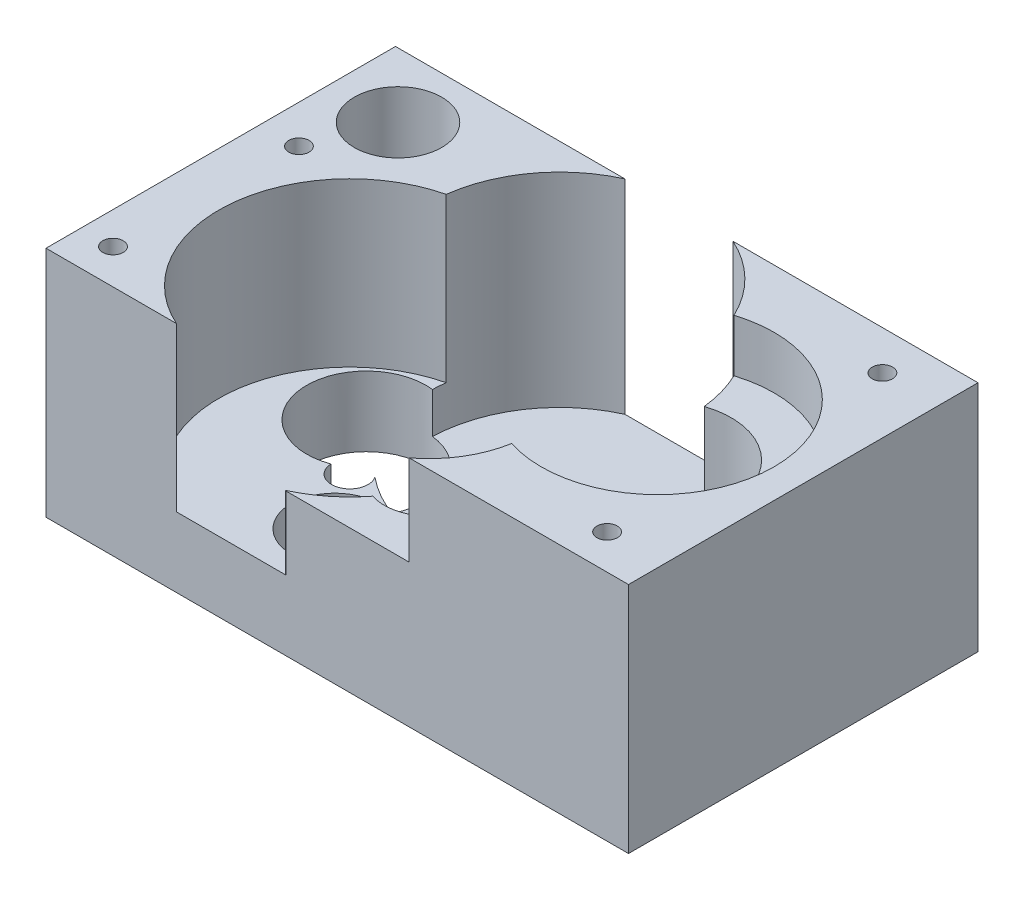
SolidWorks part; units mm, degrees
note: The reader was unsure of these and kept them because the rebuilt part matched: shared geometry of "草图3<11>", "草图3<12>", "草图3<13>", "草图3<14>", "草图5<7>".
ref_plane "前视基准面" through (0, 0, 0) normal (0, 0, 1) x (1, 0, 0)
ref_plane "上视基准面" through (0, 0, 0) normal (0, 1, 0) x (1, 0, 0)
ref_plane "右视基准面" through (0, 0, 0) normal (1, 0, 0) x (0, 0, -1)
other "Configuration Table"
sketch "草图1" plane through (0, 0, 0) normal (0, 1, 0) x (1, 0, 0)
  line L1 (0, 0) -> (20, 0)
  line L2 (0, 0) -> (0, -12)
  line L3 (0, -12) -> (20, -12)
  line L4 (20, 0) -> (20, -12)
  circle A0 centre (5, -6) radius 2.05
  circle A1 centre (6.3314, -7.9) radius 0.625
  circle A4 centre (15, -6) radius 1.05
  circle A5 centre (9.7329, -4.1) radius 0.625
  point P9 (5.9579, -9.1055)
  point P12 (9.6557, -5.4127)
  point P13 (13.834, -7.1295)
  point P14 (0, 0)
  point P17 (0, 0)
  dimension "D2" = 4.1
  dimension "D3" = 1.25
  dimension "D6" = 2.1
  dimension "D4" = 20
  dimension "D9" = 5
  dimension "D10" = 6
  dimension "D11" = 12
extrude "凸台-拉伸1" add sketch "草图1" along normal blind 1
sketch "草图3" plane through (0, 1, 0) normal (0, 1, 0) x (1, 0, 0)
  line L1 (0, 0) -> (20, 0)
  line L2 (0, 0) -> (0, -12)
  line L3 (0, -12) -> (20, -12)
  line L4 (20, 0) -> (20, -12)
  circle A0 centre (5, -6) radius 2.05
  arc A1 (6.5674, -7.3213) -> (5.7069, -7.9243) centre (5, -6) ccw construction
  circle A2 centre (6.3314, -7.9) radius 0.625
  arc A3 (5.7069, -7.9243) -> (6.5674, -7.3213) centre (6.3314, -7.9) ccw construction
  circle A4 centre (9.7329, -4.1) radius 4.5
  circle A5 centre (9.7329, -4.1) radius 0.6 construction
  circle A6 centre (6.3314, -7.9) radius 4.5
  circle A7 centre (10.3527, -9.2133) radius 1.525
  circle A8 centre (15, -6) radius 1.05
  circle A9 centre (15, -6) radius 2.525
  circle A11 centre (15, -6) radius 4
  circle A12 centre (10.3527, -9.2133) radius 3.5
  circle A13 centre (15, -6) radius 1.05 construction
  circle M4 centre (15, -6) radius 1.05
  line M5 (0, 0) -> (0, -12)
  line M6 (0, -12) -> (20, -12)
  line M7 (20, -12) -> (20, 0)
  line M8 (20, 0) -> (0, 0)
  arc M9 (5.7069, -7.9243) -> (6.5674, -7.3213) centre (5, -6) cw
  arc M10 (6.5674, -7.3213) -> (5.7069, -7.9243) centre (6.3314, -7.9) cw
  dimension "D1" = 9
  dimension "D2" = 8
  dimension "D3" = 7
  dimension "D4" = 2.1
  dimension "D5" = 5.05
extrude "凸台-拉伸5" add sketch "草图3" along normal blind 1.4 contours A6 A4 M8 M5 M6 | A12 A4 A6 L3 M9 M10 | A4 A12 A6 A7 | A4 A7 A6 | A6 A7 A4 | L3 A12 A11 A4 A7 A6 | A11 A12 A9 A4 | A9 A12 A4 | A12 A9 A4 M4 | A12 A11 A4 A9 | A12 A4 A11 M6 M7 M8 | A12 A6 M6
extrude "凸台-拉伸6" add sketch "草图3<11>" along normal blind 1.4 from surface at 1.4 contours A6 A4 M8 M5 M6 | A11 A12 A9 A4 | A12 A11 A4 A9 | A12 A4 A11 M6 M7 M8 | L3 A12 A11 A4 A7 A6 | A6 A7 A4
sketch "草图3<11>" plane through (0, 1, 0) normal (0, 1, 0) x (1, 0, 0) same geometry as "草图3"
extrude "凸台-拉伸7" add sketch "草图3<12>" along normal blind 1.1 from surface at 2.8 contours A6 A4 M8 M5 M6 | L3 A12 A11 A4 A7 A6 | A12 A4 A11 M6 M7 M8 | A12 A11 A4 A9 | A11 A12 A9 A4
sketch "草图3<12>" plane through (0, 1, 0) normal (0, 1, 0) x (1, 0, 0) same geometry as "草图3"
extrude "凸台-拉伸8" add sketch "草图3<13>" along normal blind 1.3 from surface contours A6 A4 M8 M5 M6 | A12 A4 A11 M6 M7 M8 | A12 A11 A4 A9
sketch "草图3<13>" plane through (0, 1, 0) normal (0, 1, 0) x (1, 0, 0) same geometry as "草图3"
extrude "凸台-拉伸9" add sketch "草图3<14>" along normal blind 1.8 from surface at 5.2 contours A6 A4 M8 M5 M6 | A12 A4 A11 M6 M7 M8 starting at face at (2.8287, 6.2, 5.381)
sketch "草图3<14>" plane through (0, 1, 0) normal (0, 1, 0) x (1, 0, 0) same geometry as "草图3"
sketch "草图5" plane through (0, 0, 0) normal (0, 1, 0) x (1, 0, 0)
  circle A0 centre (2.3, -2.2142) radius 0.8
  circle A1 centre (7.7, -9.7858) radius 0.8
  circle A4 centre (2.3, -2.2142) radius 1.5
  circle A5 centre (7.7, -9.7858) radius 1.5
  dimension "D1" = 1.6
  dimension "D2" = 3
extrude "切除-拉伸9" cut sketch "草图5" along normal through all contours A1 | A0
extrude "切除-拉伸10" cut sketch "草图5<7>" against normal offset from surface (7 mm away) 1 from surface at 8 contours A5 | A4 up to face at (7.7, 0, 10.5858) starting at face at (2.3, 8, 3.0142)
sketch "草图5<7>" plane through (0, 0, 0) normal (0, 1, 0) x (1, 0, 0) same geometry as "草图5"
sketch "草图6" plane through (0, 8, 0) normal (0, 1, 0) x (1, 0, 0)
  circle A0 centre (18.0672, -1.3489) radius 0.35
  circle A1 centre (18.0672, -10.8015) radius 0.35
  circle A2 centre (1.3106, -4.6263) radius 0.35
  circle A3 centre (1.1013, -10.8015) radius 0.35
  dimension "D1" = 0.7
extrude "切除-拉伸11" cut sketch "草图6" against normal blind 2
